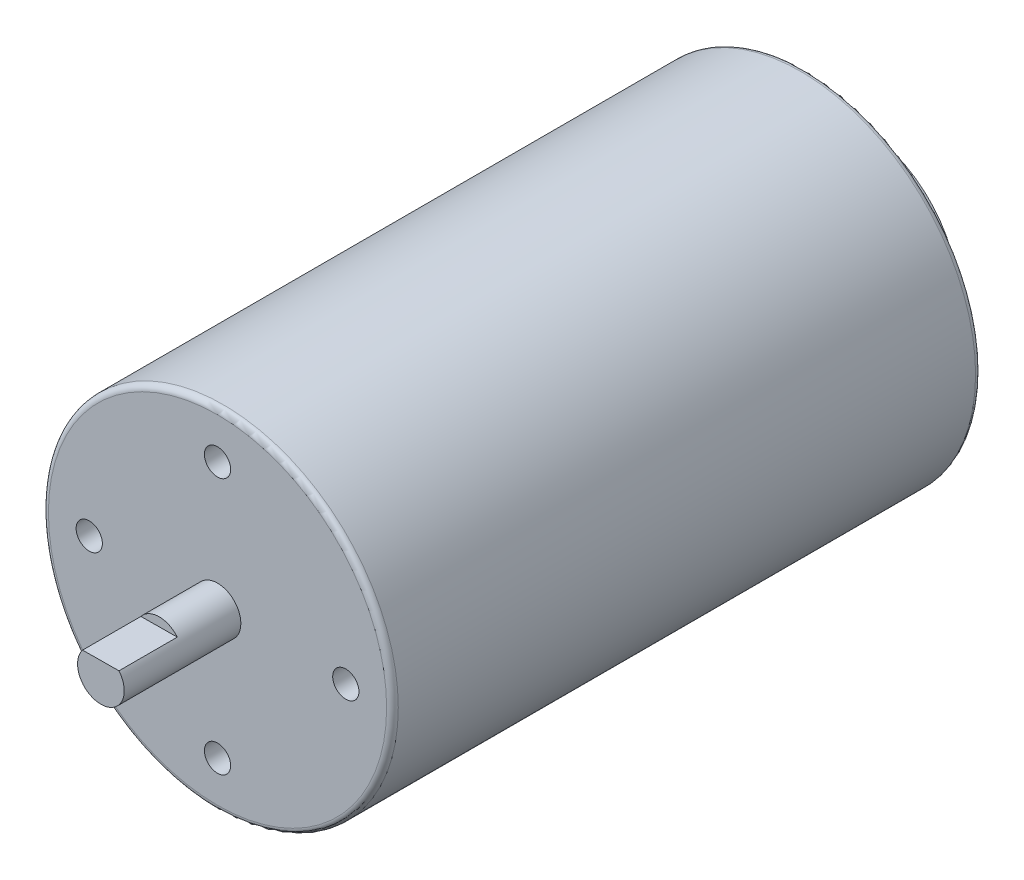
SolidWorks part; units mm, degrees
ref_plane "Plan de face" through (0, 0, 0) normal (1, 0, 0) x (0, 1, 0)
ref_plane "Plan de dessus" through (0, 0, 0) normal (0, 0, 1) x (0, 1, 0)
ref_plane "Plan de droite" through (0, 0, 0) normal (0, 1, 0) x (-1, 0, 0)
sketch "Esquisse1" plane through (0, 0, 0) normal (0, 0, 1) x (0, 1, 0)
  circle A0 centre (0, 0) radius 30
  dimension "D1" = 60
extrude "Boss.-Extru.1" add sketch "Esquisse1" along normal blind 101
sketch "Esquisse2" plane through (0, 0, 101) normal (0, 0, 1) x (1, 0, 0)
  circle A0 centre (0, 0) radius 4
  dimension "D1" = 8
extrude "Boss.-Extru.2" add sketch "Esquisse2" along normal blind 20
sketch "Esquisse3" plane through (0, 0, 121) normal (0, 0, 1) x (1, 0, 0)
  line L0 (-3.1427, 2.4746) -> (3.102, 2.5254)
  arc A0 (-3.1427, 2.4746) -> (3.102, 2.5254) centre (0, 0) cw
  circle A1 centre (0, 0) radius 4 construction
  point P6 (-0.0203, 2.5)
  dimension "D1" = 2.5
extrude "Enlèv. mat.-Extru.1" cut sketch "Esquisse3" against normal blind 10
fillet "Congé1" radius 1 2 edges at (30, 0, 0) (30, 0, 101)
sketch "Esquisse4" plane through (0, 0, 0) normal (0, 0, -1) x (1, 0, 0)
  circle A0 centre (0, 0) radius 17
  dimension "D1" = 34
extrude "Boss.-Extru.3" add sketch "Esquisse4" along normal blind 9
sketch "Esquisse5" plane through (0, 0, 101) normal (0, 0, 1) x (1, 0, 0)
  circle A0 centre (0, 22) radius 2.25
  circle A2 centre (22, 0) radius 2.25
  circle A3 centre (0, -22) radius 2.25
  circle A4 centre (-22, 0) radius 2.25
  dimension "D1" = 4.5
  dimension "D2" = 22
  dimension "D3" = 4
extrude "Enlèv. mat.-Extru.2" cut sketch "Esquisse5" against normal blind 9
